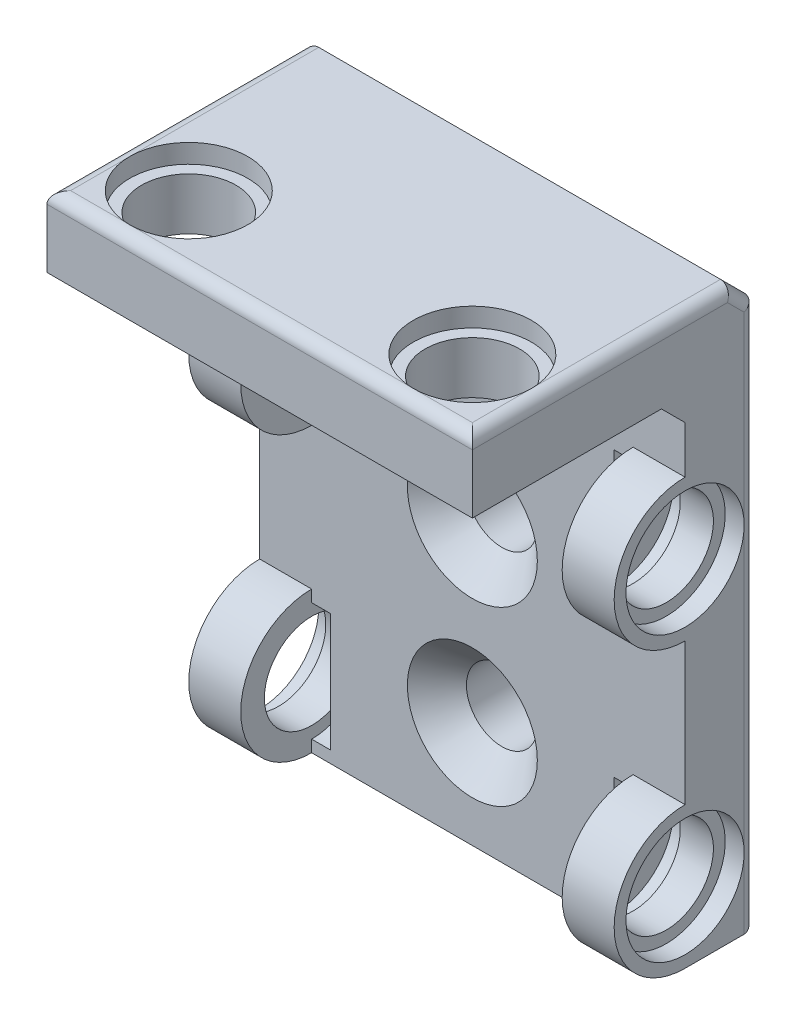
SolidWorks part; units mm, degrees
ref_plane "Front Plane" through (0, 0, 0) normal (0, 0, 1) x (1, 0, 0)
ref_plane "Top Plane" through (0, 0, 0) normal (0, 1, 0) x (1, 0, 0)
ref_plane "Right Plane" through (0, 0, 0) normal (1, 0, 0) x (0, 0, -1)
sketch "Sketch1" plane through (0, 0, 0) normal (0, 0, 1) x (1, 0, 0)
  line L1 (9, 15) -> (-9, 15)
  line L2 (9, 15) -> (9, -15)
  line L3 (9, -15) -> (-9, -15)
  line L4 (-9, 15) -> (-9, -15)
  line L5 (9, 15) -> (-9, -15) construction
  line L6 (9, -15) -> (-9, 15) construction
  line L7 (-9, -15) -> (9, -15)
  line L8 (-9, -15) -> (-9, -10.8109)
  line L10 (9, -15) -> (9, -10.8109)
  point P0 (0, 0)
  dimension "D1" = 18
  dimension "D2" = 30
extrude "Boss-Extrude1" add sketch "Sketch1" along normal blind 3 contours L4 L3 L2 L1
sketch "Sketch2" plane through (0, 0, 3) normal (0, 0, 1) x (1, 0, 0)
  line L0 (6.0473, 6) -> (11.6863, 6) construction
  line L3 (6, 8.5) -> (6.8, 8.5)
  line L4 (6.8, 8.5) -> (6.8, 8)
  line L5 (6.8, 8) -> (8.2, 8)
  line L6 (8.2, 8) -> (8.2, 8.5)
  line L7 (8.2, 8.5) -> (9, 8.5)
  line L8 (9, 8.5) -> (9, 6)
  line L9 (9, 6) -> (6, 6)
  line L10 (6, 6) -> (6, 8.5)
  line L11 (6, 8.5) -> (5.9996, 7.7527)
  line L12 (9, 15) -> (9, -15) construction
  line L13 (0, 0) -> (15.3731, 0) construction
  line L17 (9, 8.5) -> (9, 9)
  line L18 (9, 9) -> (6.8, 9)
  line L19 (6.8, 9) -> (6.8, 8.5)
  dimension "D1" = 6
  dimension "D2" = 2.5
  dimension "D3" = 0.8
  dimension "D4" = 0.5
  dimension "D5" = 1.4
  dimension "D6" = 0.5
  dimension "D7" = 0.8
  dimension "D8" = 0.5
revolve "Cut-Revolve1" cut sketch "Sketch2" angle 360 about L0
revolve "Revolve1" add sketch "Sketch2<3>" angle 360 about L0 region at (7.7444, 8.5556, 3)
sketch "Sketch2<3>" plane through (0, 0, 3) normal (0, 0, 1) x (1, 0, 0) same geometry as "Sketch2"
mirror "Mirror1" about plane through (0, 0, 0) normal (1, 0, 0) of "Revolve1", "Cut-Revolve1"
mirror "Mirror2" about plane through (0, 0, 0) normal (0, 1, 0) of "Mirror1"
sketch "Sketch3" plane through (0, 0, 3) normal (0, 0, 1) x (1, 0, 0)
  line L1 (-9, 15) -> (9, 15)
  line L2 (-9, 15) -> (-9, 12)
  line L3 (-9, 12) -> (9, 12)
  line L4 (9, 15) -> (9, 12)
  dimension "D1" = 3
extrude "Boss-Extrude2" add sketch "Sketch3" along normal blind 9
sketch "Sketch4" plane through (0, 15, 0) normal (0, 1, 0) x (1, 0, 0)
  line L0 (0, -12) -> (0, 2.8555) construction
  line L1 (9, -12) -> (-9, -12) construction
  line L2 (-12.1563, -9) -> (14.1781, -9) construction
  point P5 (6, -9)
  point P6 (-6, -9)
  dimension "D1" = 3
  dimension "D2" = 6
  dimension "D3" = 6
hole_wizard "CBORE for M5 Hex Head Bolt1" positions "Sketch6" profile "Sketch7" counterbore size "M5" standard "ANSI Metric"
sketch "Sketch6" plane through (0, 15, 0) normal (0, 1, 0) x (1, 0, 0)
  point P0 (-6, -9)
  point P3 (6, -9)
sketch "Sketch7" plane through (-6, 15, 9) normal (1, 0, 0) x (0, 0, 1)
  line L0 (0, 0) -> (0, 5.1781)
  line L1 (0, 5.1781) -> (2, 4)
  line L2 (2, 4) -> (2, 0.8)
  line L3 (2, 0.8) -> (2.5, 0.8)
  line L4 (2.5, 0.8) -> (2.5, 0)
  line L5 (2.5, 0) -> (0, 0)
  line L10 (0, 5.1781) -> (-2, 4) construction
  line L11 (0, -6.35) -> (0, 107.95) construction
  dimension "Hole Dia." = 4
  dimension "Hole Depth" = 4
  dimension "C'Bore Dia." = 5
  dimension "C'Bore Depth" = 0.8
  dimension "Drill Angle" = 119
chamfer "Chamfer1" distance 1 angle 45 2 edges at (0, 12, 3) (0, 15, 0)
sketch "Sketch8" plane through (0, 0, 0) normal (0, 0, -1) x (-1, 0, 0)
  line L0 (-9, 14) -> (-9, -15) construction
  line L1 (9, -15) -> (-9, -15)
  line L2 (9, -15) -> (9, -9)
  line L3 (9, -9) -> (-9, -9)
  line L4 (-9, -15) -> (-9, -9)
  dimension "D1" = 6
extrude "Cut-Extrude1" cut sketch "Sketch8" against normal blind 12 contours L3 L4 L1 L2
fillet "Fillet2" radius 0.5 8 edges at (0, -9, 0) (-9, 2.5, 0) (-9, 14.5, 0.5) (-9, 15, 6.5) (9, 2.5, 0) (9, 14.5, 0.5) (0, 15, 12) (9, 15, 6.5)
sketch "Sketch9" plane through (0, 0, 0) normal (0, 0, -1) x (-1, 0, 0)
  line L0 (0, -8.5) -> (0, 16.5413) construction
  line L1 (-8.5, -8.5) -> (8.5, -8.5) construction
  point P5 (0, -4.5)
  point P6 (0, 2.8)
  dimension "D1" = 4
  dimension "D2" = 7.3
hole_wizard "Ø3.0mm Dowel Hole1" positions "Sketch11" profile "Sketch12" hole size "Ø3.0" standard "DIN"
sketch "Sketch11" plane through (0, 0, 0) normal (0, 0, -1) x (-1, 0, 0)
  point P0 (0, -4.5)
  point P3 (0, 2.8)
sketch "Sketch12" plane through (0, -4.5, 0) normal (1, 0, 0) x (0, 1, 0)
  line L0 (0, 0) -> (0, 10.9013)
  line L1 (0, 10.9013) -> (1.5, 10)
  line L2 (1.5, 10) -> (1.5, 0)
  line L5 (1.5, 0) -> (0, 0)
  line L10 (0, 10.9013) -> (-1.5, 10) construction
  line L11 (0, -6.35) -> (0, 107.95) construction
  dimension "Hole Dia." = 3
  dimension "Hole Depth" = 10
  dimension "Drill Angle" = 118
sketch "Sketch13" plane through (0, 0, 3) normal (0, 0, 1) x (1, 0, 0)
  circle A0 centre (0, 2.8) radius 2.75
  circle A1 centre (0, -4.5) radius 2.75
  dimension "D1" = 5.5
  dimension "D2" = 5.5
extrude "Cut-Extrude2" cut sketch "Sketch13" against normal blind 10 draft 45
